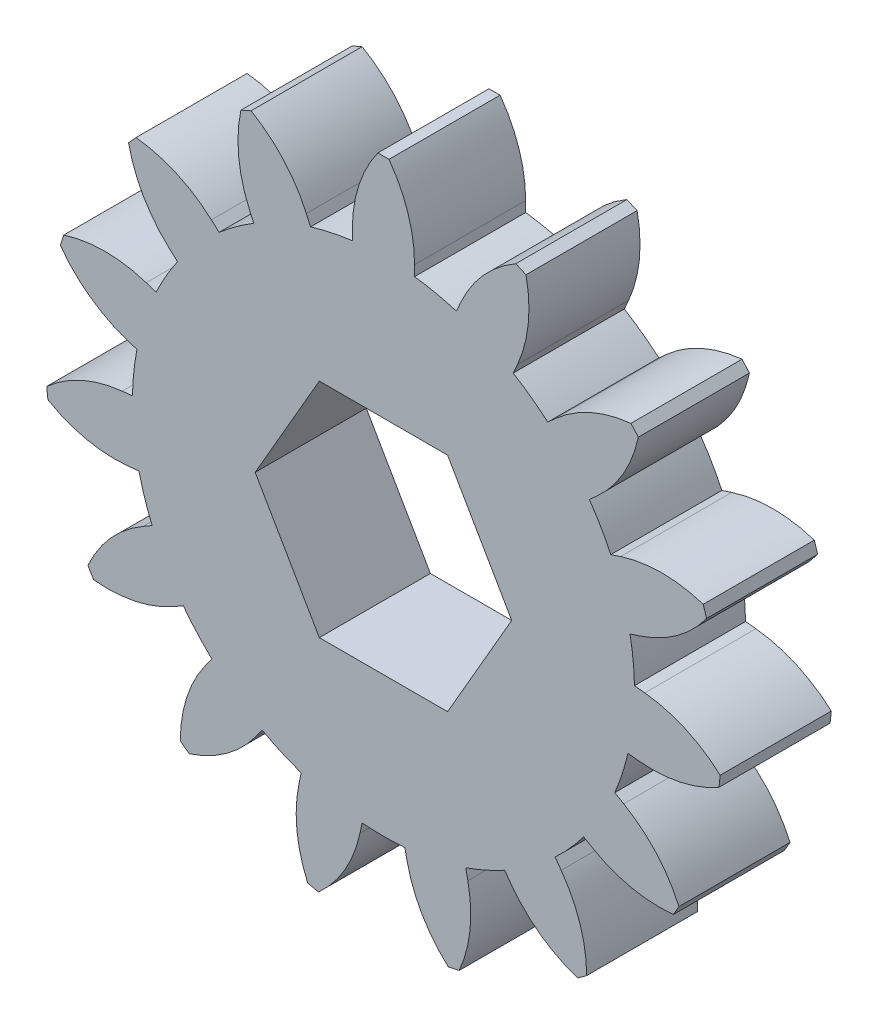
SolidWorks part; units mm, degrees
material "Magnesium Alloy"
ref_plane "Front Plane" through (0, 0, 0) normal (0, 0, 1) x (1, 0, 0)
ref_plane "Top Plane" through (0, 0, 0) normal (0, 1, 0) x (1, 0, 0)
ref_plane "Right Plane" through (0, 0, 0) normal (1, 0, 0) x (0, 0, -1)
sketch "Sketch1" plane through (0, 0, 0) normal (0, 0, 1) x (1, 0, 0)
  line L1 (3.6662, 6.35) -> (-3.6662, 6.35)
  line L2 (-3.6662, 6.35) -> (-7.3323, 0)
  line L3 (-7.3323, 0) -> (-3.6662, -6.35)
  line L4 (-3.6662, -6.35) -> (3.6662, -6.35)
  line L5 (3.6662, -6.35) -> (7.3323, 0)
  line L6 (7.3323, 0) -> (3.6662, 6.35)
  circle A0 centre (0, 0) radius 14.351
  circle A1 centre (0, 0) radius 6.35 construction
  dimension "D1" = 12.7
  dimension "D2" = 28.702
extrude "Boss-Extrude1" add sketch "Sketch1" along normal blind 6.35
sketch "Sketch2" plane through (0, 0, 6.35) normal (0, 0, 1) x (1, 0, 0)
  line L0 (-1.778, 14.2404) -> (-1.778, 17.4154)
  line L1 (-1.778, 17.4154) -> (-0.3175, 19.3204)
  line L2 (-0.3175, 19.3204) -> (0.3175, 19.3204)
  line L3 (0.3175, 19.3204) -> (1.778, 17.4154)
  line L4 (1.778, 17.4154) -> (1.778, 14.2404)
  line L5 (0, -55) -> (0, 55) construction
  line L6 (-1.778, 14.2404) -> (1.778, 14.2404)
  circle A0 centre (0, 0) radius 14.351 construction
  dimension "D1" = 0.635
  dimension "D2" = 3.175
  dimension "D3" = 1.905
  dimension "D4" = 1.778
  dimension "D5" = 1.778
extrude "Boss-Extrude2" add sketch "Sketch2" against normal blind 6.35
pattern_circular "CirPattern1" count 15 over 360 about axis through (0, 0, 6.35) along (0, 0, -1) of "Boss-Extrude2"
fillet "Fillet2" radius 7.62 30 edges at (14.1932, -10.2475, 3.175) (17.1125, 3.6907, 3.175) (-8.7981, -15.1345, 3.175) (8.7981, -15.1345, 3.175) (17.1342, -3.5887, 3.175) (1.8817, -17.4045, 3.175) (-5.36, -16.6652, 3.175) (-14.1932, -10.2475, 3.175) (-17.1342, -3.5887, 3.175) (-17.1125, 3.6907, 3.175) (-14.1319, 10.3319, 3.175) (-8.7078, 15.1866, 3.175) (-17.5059, -0.0521, 3.175) (-15.9712, -7.1679, 3.175) (-11.675, -13.0443, 3.175) (-1.8817, -17.4045, 3.175) (5.36, -16.6652, 3.175) (11.675, -13.0443, 3.175) (15.9712, -7.1679, 3.175) (14.1319, 10.3319, 3.175) (8.7078, 15.1866, 3.175) (5.4592, 16.633, 3.175) (17.5059, -0.0521, 3.175) (16.0136, 7.0726, 3.175) (11.7525, 12.9745, 3.175) (-16.0136, 7.0726, 3.175) (-11.7525, 12.9745, 3.175) (-5.4592, 16.633, 3.175) (1.778, 17.4154, 3.175) (-1.778, 17.4154, 3.175)
